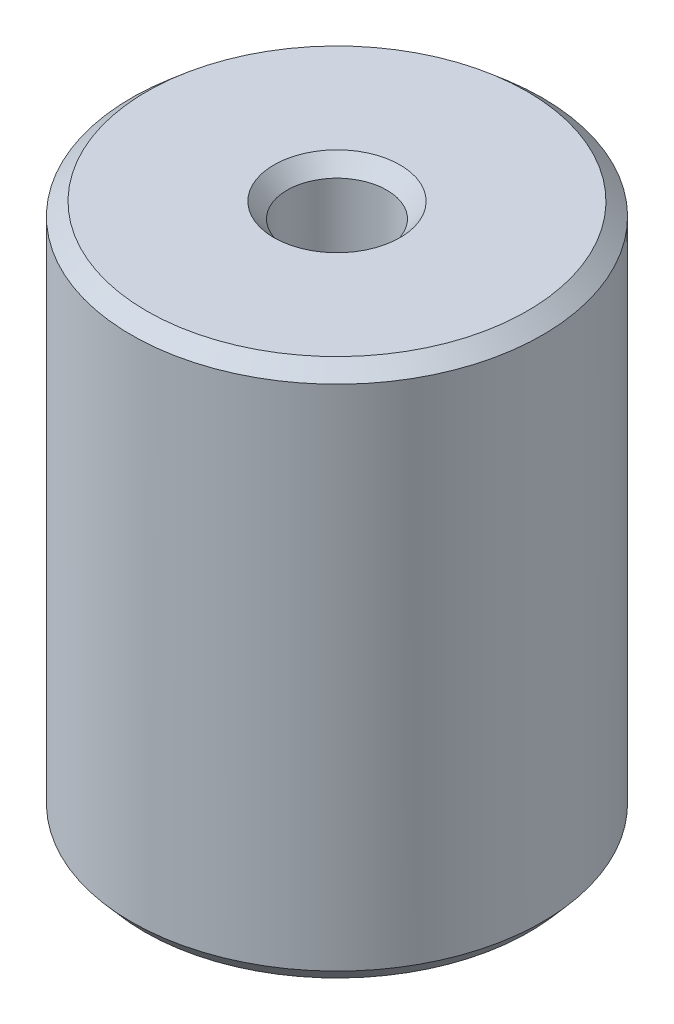
SolidWorks part; units mm, degrees
ref_plane "Front Plane" through (0, 0, 0) normal (0, 0, 1) x (1, 0, 0)
ref_plane "Top Plane" through (0, 0, 0) normal (0, 1, 0) x (1, 0, 0)
ref_plane "Right Plane" through (0, 0, 0) normal (1, 0, 0) x (0, 0, -1)
sketch "Sketch1" plane through (0, 0, 0) normal (0, 1, 0) x (1, 0, 0)
  circle A0 centre (0, 0) radius 5
  dimension "SLEEVE_OD" = 10
extrude "Boss-Extrude1" add sketch "Sketch1" along normal blind 13.0596
sketch "Sketch2" plane through (0, 0, 0) normal (0, 1, 0) x (1, 0, 0)
  circle A0 centre (0, 0) radius 1.2141
  dimension "BORE_D" = 2.4282
extrude "Cut-Extrude1" cut sketch "Sketch2" along normal through all
chamfer "Chamfer1" distance 0.3204 angle 49.219 4 edges at (0, 13.0596, 1.2141) (0, 0, 1.2141) (0, 0, 5) (0, 13.0596, 5) first distance on face at (0, 13.0596, 1.2141) first distance on face at (0, 0, 1.2141) first distance on face at (0, 13.0596, 5)
